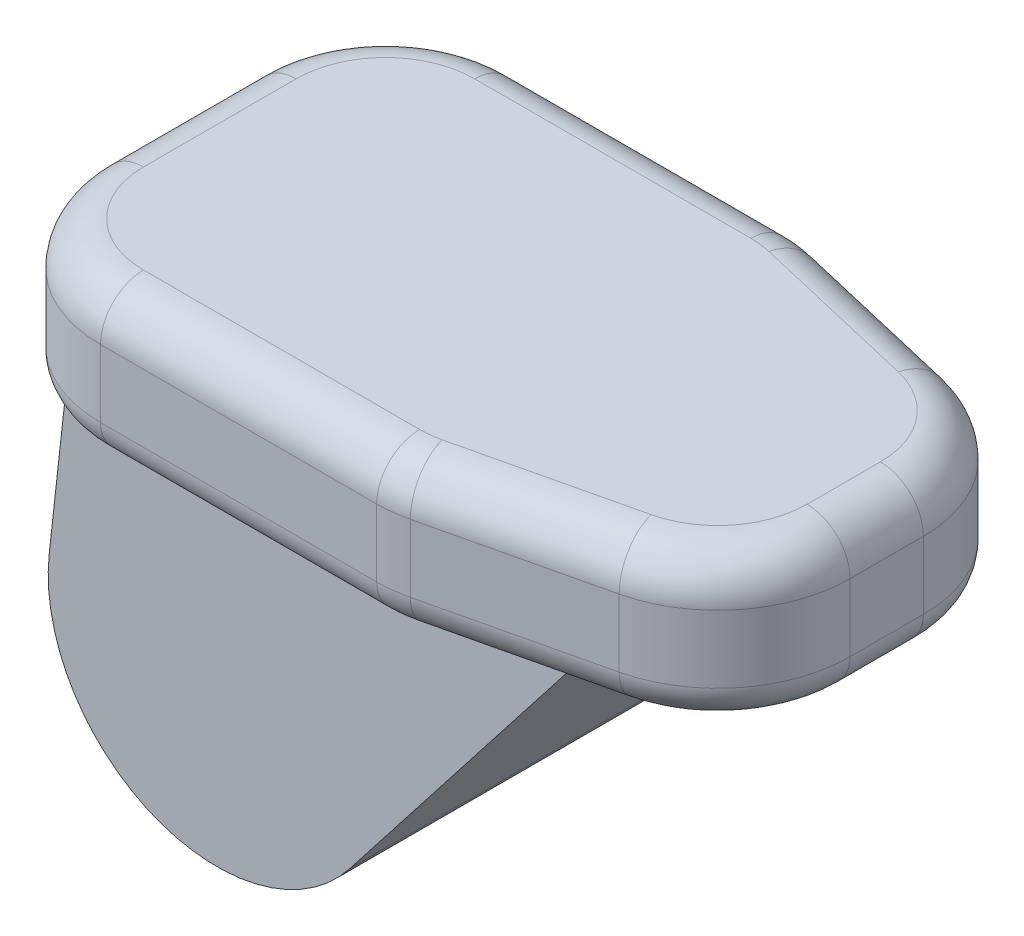
SolidWorks part; units mm, degrees
ref_plane "Front Plane" through (0, 0, 0) normal (0, 0, 1) x (1, 0, 0)
ref_plane "Top Plane" through (0, 0, 0) normal (0, 1, 0) x (1, 0, 0)
ref_plane "Right Plane" through (0, 0, 0) normal (1, 0, 0) x (0, 0, -1)
sketch "Gripper Block Sketch" plane through (0, 0, 0) normal (0, 0, 1) x (1, 0, 0)
  line L0 (0, 0) -> (0, 69.1123) construction
  line L1 (-61.4071, 69.1123) -> (141.0683, 69.1123)
  line L2 (141.0683, 69.1123) -> (54.1367, -42.2574)
  line L3 (-61.4071, 69.1123) -> (-68.2549, 7.5982)
  arc A0 (54.1367, -42.2574) -> (-68.2549, 7.5982) centre (0, 0) ccw construction
  arc A1 (-68.2549, 7.5982) -> (54.1367, -42.2574) centre (0, 0) ccw
  point P6 (0, 69.1123)
  dimension "D2" = 137.353
  dimension "D1" = 69.1123
extrude "Gripper Block Extrude" add sketch "Gripper Block Sketch" along normal up to surface (65 mm away) and the other way up to surface (65 mm away)
sketch "Gripper Pad Sketch" plane through (0, 69.1123, 0) normal (0, 1, 0) x (1, 0, 0)
  line L0 (-61.4071, -65) -> (-65.5412, -69.1341) construction
  line L1 (-61.4071, 65) -> (-65.5412, 69.1341) construction
  line L8 (207.6286, -14.9185) -> (207.6286, 14.9185)
  line L10 (-81.312, -31.0599) -> (-81.312, 31.0599)
  line L11 (84.9364, -84.905) -> (-27.4669, -84.905)
  line L12 (-31.312, 0) -> (135.3412, 0) construction
  line L13 (166.0744, -67.342) -> (97.2273, -83.4834)
  line L14 (84.9364, -84.905) -> (207.6286, -84.905) construction
  line L16 (207.6286, -84.905) -> (207.6286, -14.9185) construction
  line L21 (-81.312, -31.0599) -> (-81.312, -84.905) construction
  line L22 (-81.312, -84.905) -> (-27.4669, -84.905) construction
  line L23 (207.6286, 84.905) -> (207.6286, 14.9185) construction
  line L24 (84.9364, 84.905) -> (207.6286, 84.905) construction
  line L25 (-81.312, 84.905) -> (-27.4669, 84.905) construction
  line L26 (-81.312, 31.0599) -> (-81.312, 84.905) construction
  line L27 (166.0744, 67.342) -> (97.2273, 83.4834)
  line L28 (135.3412, 0) -> (207.6286, 0) construction
  line L29 (-31.312, 0) -> (-81.312, 0) construction
  line L30 (84.9364, 84.905) -> (-27.4669, 84.905)
  line L31 (28.7348, 84.905) -> (28.7348, 65) construction
  arc A0 (207.6286, -14.9185) -> (166.0744, -67.342) centre (153.7835, -14.9185) cw
  arc A1 (97.2273, -83.4834) -> (84.9364, -84.905) centre (84.9364, -31.0599) cw
  arc A2 (-81.312, -31.0599) -> (-27.4669, -84.905) centre (-27.4669, -31.0599) ccw
  arc A4 (207.6286, 14.9185) -> (166.0744, 67.342) centre (153.7835, 14.9185) ccw
  arc A5 (97.2273, 83.4834) -> (84.9364, 84.905) centre (84.9364, 31.0599) ccw
  arc A6 (-81.312, 31.0599) -> (-27.4669, 84.905) centre (-27.4669, 31.0599) cw
  dimension "D2" = 50
  dimension "D3" = 19.905
  dimension "D1" = 53.8451
  dimension "D5" = 53.8451
  dimension "D4" = 72.2873
  dimension "D6" = 288.9406
extrude "Gripper Pad Extrude" add sketch "Gripper Pad Sketch" along normal blind 60
fillet "Fillet1" radius 15 12 edges at (28.7348, 69.1123, 84.905) (91.1229, 69.1123, 84.5484) (131.6509, 69.1123, 75.4127) (195.98, 69.1123, 48.3661) (207.6286, 69.1123, 0) (195.98, 69.1123, -48.3661) (131.6509, 69.1123, -75.4127) (91.1229, 69.1123, -84.5484) (28.7348, 69.1123, -84.905) (-65.5412, 69.1123, -69.1341) (-81.312, 69.1123, 0) (-65.5412, 69.1123, 69.1341)
fillet "Fillet2" radius 17.5 12 edges at (-81.312, 129.1123, 0) (-65.5412, 129.1123, -69.1341) (28.7348, 129.1123, -84.905) (91.1229, 129.1123, -84.5484) (131.6509, 129.1123, -75.4127) (195.98, 129.1123, -48.3661) (207.6286, 129.1123, 0) (195.98, 129.1123, 48.3661) (131.6509, 129.1123, 75.4127) (91.1229, 129.1123, 84.5484) (28.7348, 129.1123, 84.905) (-65.5412, 129.1123, 69.1341)
equation "\"D2@Gripper Block Sketch\" = \"D1@Stem Block Sketch@Gripper Segment 02<1>.Part\""
